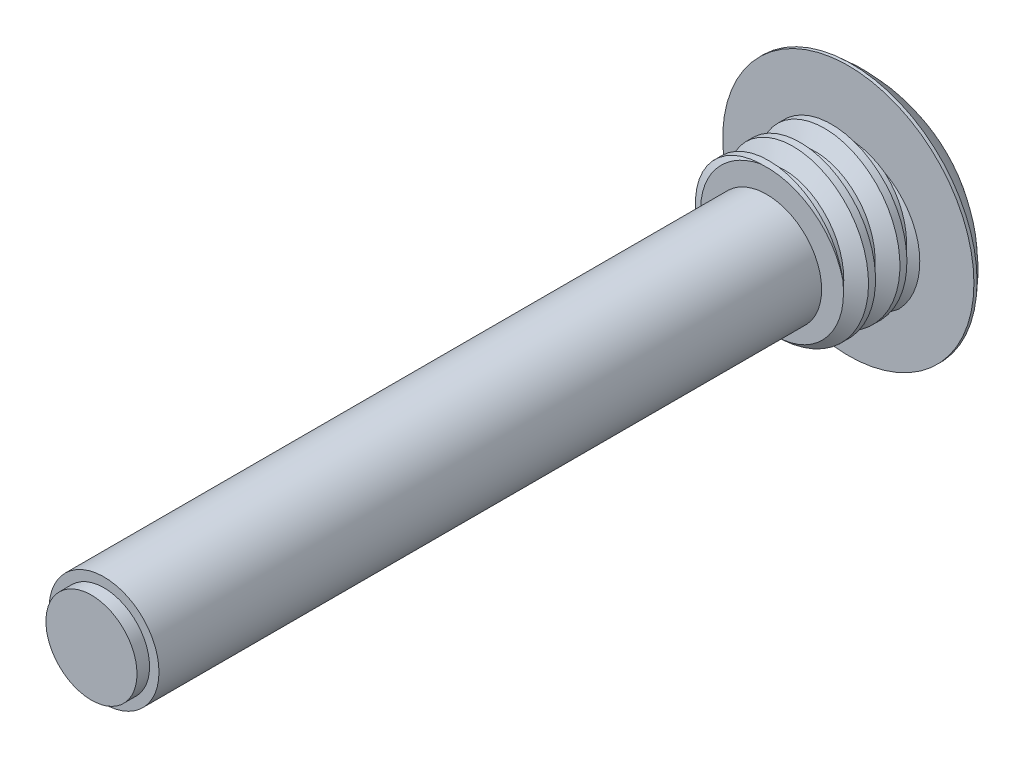
SolidWorks part; units mm, degrees
ref_plane "Front Plane" through (0, 0, 0) normal (0, 0, 1) x (1, 0, 0)
ref_plane "Top Plane" through (0, 0, 0) normal (0, 1, 0) x (1, 0, 0)
ref_plane "Right Plane" through (0, 0, 0) normal (1, 0, 0) x (0, 0, -1)
sketch "Sketch2" plane through (0, 0, 0) normal (0, 0, 1) x (1, 0, 0)
  circle A0 centre (0, 0) radius 3.175
curve "Helix/Spiral1" pitch 1.27 height 3.302 radius 3.175 left hand yes centre (0, 0, 0) axis (0, 0, 1) start towards (0, 1, 0)
sketch "Sketch3" plane through (0, 0, 0) normal (0, 0, 1) x (1, 0, 0)
  circle A0 centre (0, 0) radius 3.175
extrude "Boss-Extrude1" add sketch "Sketch3" along normal blind 3.302 contours A0
sketch "Sketch5" plane through (0, 0, 0) normal (1, 0, 0) x (0, 0, -1)
  line L0 (0.127, 2.54) -> (0.4936, 3.175)
  line L1 (0.4936, 3.175) -> (-0.4936, 3.175)
  line L2 (-0.4936, 3.175) -> (-0.127, 2.54)
  line L3 (-0.127, 2.54) -> (0.127, 2.54)
  line L4 (0, 3.175) -> (0, 2.54) construction
  dimension "D1" = 0.635
  dimension "D2" = 0.254
  dimension "D3" = 60
sweep "Cut-Sweep1" cut profiles "Sketch5" path "Helix/Spiral1" align with end faces yes
sketch "Sketch10" plane through (0, 0, 3.302) normal (0, 0, 1) x (1, 0, 0)
  circle A0 centre (0, 0) radius 2.2225
  dimension "D1" = 4.445
extrude "Boss-Extrude5" add sketch "Sketch10" along normal blind 26.797
sketch "Sketch9" plane through (0, 0, 0) normal (0, 0, 1) x (1, 0, 0)
  circle A0 centre (0, 0) radius 5.08
  dimension "D1" = 10.16
extrude "Boss-Extrude4" add sketch "Sketch9" against normal blind 0.127
dome "Dome3" faces to dome 1 distance 2.38 reverse direction no elliptical dome no face at (5.08, 0, -0.127) parameters "D1"=2.38
sketch "Sketch11" plane through (0, 0, 30.099) normal (0, 0, 1) x (1, 0, 0)
  circle A0 centre (0, 0) radius 1.8415
  dimension "D1" = 3.683
extrude "Boss-Extrude6" add sketch "Sketch11" along normal blind 0.508
